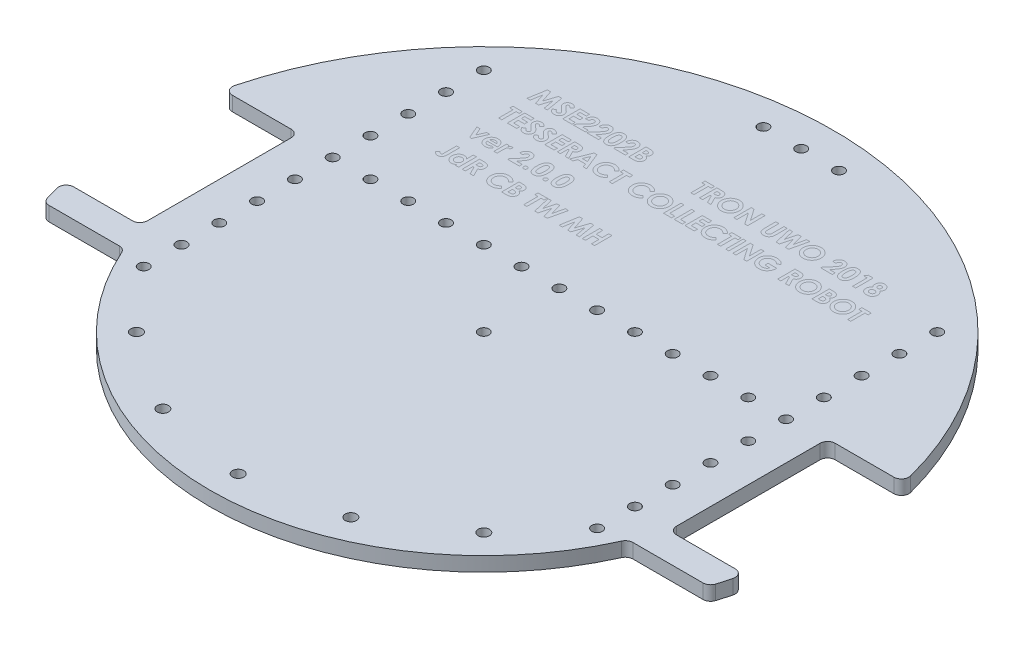
SolidWorks part; units mm, degrees
material "Balsa"
ref_plane "Front Plane" through (0, 0, 0) normal (0, 0, 1) x (1, 0, 0)
ref_plane "Top Plane" through (0, 0, 0) normal (0, 1, 0) x (1, 0, 0)
ref_plane "Right Plane" through (0, 0, 0) normal (1, 0, 0) x (0, 0, -1)
sketch "Sketch1" plane through (0, 0, 0) normal (0, 1, 0) x (1, 0, 0)
  circle A0 centre (0, 0) radius 117.475
  dimension "D1" = 234.95
extrude "Boss-Extrude1" add sketch "Sketch1" against normal blind 4.826
sketch "Sketch3" plane through (0, 0, 0) normal (0, 1, 0) x (1, 0, 0)
  line L1 (-114.4075, 26.67) -> (-88.9, 26.67)
  line L2 (0, -92.075) -> (0, -117.475)
  line L3 (-88.9, -26.67) -> (-88.9, 26.67)
  line L4 (0, 0) -> (-88.9, 0) construction
  line L5 (0, 0) -> (0, -117.475) construction
  line L6 (0, 0) -> (0, 117.475) construction
  line L8 (-88.9, -26.67) -> (-114.4075, -26.67)
  line L10 (-84.6624, -36.195) -> (-111.76, -36.195)
  arc A0 (-114.4075, 26.67) -> (-114.4075, -26.67) centre (0, 0) ccw
  circle A1 centre (0, 0) radius 117.475 construction
  arc A3 (-84.6624, -36.195) -> (0, -92.075) centre (0, 0) ccw
  arc A4 (-111.76, -36.195) -> (0, -117.475) centre (0, 0) ccw
  dimension "D1" = 88.9
  dimension "D2" = 53.34
  dimension "D4" = 9.525
  dimension "D5" = 25.4
extrude "Cut-Extrude4" cut sketch "Sketch3" against normal through all
fillet "Fillet1" radius 2.54 6 edges at (-114.4075, -2.413, 26.67) (-114.4075, -2.413, -26.67) (-88.9, -2.413, 26.67) (-88.9, -2.413, -26.67) (-111.76, -2.413, 36.195) (-84.6624, -2.413, 36.195)
mirror "Mirror1" about plane through (0, 0, 0) normal (1, 0, 0) of "Cut-Extrude4", "Fillet1"
sketch "Sketch4" plane through (0, 0, 0) normal (0, 1, 0) x (1, 0, 0)
  line L0 (-76.2, 38.1) -> (-76.2, 25.4) construction
  line L1 (-76.2, 25.4) -> (-76.2, 12.7) construction
  line L2 (-76.2, 12.7) -> (-76.2, 0) construction
  line L3 (-76.2, 0) -> (-76.2, -12.7) construction
  line L4 (-76.2, -12.7) -> (-76.2, -25.4) construction
  line L5 (-76.2, -25.4) -> (-76.2, -38.1) construction
  line L6 (0, 0) -> (-76.2, 0) construction
  line L12 (-76.2, 76.2) -> (-76.2, 63.5) construction
  line L13 (-76.2, 63.5) -> (-76.2, 50.8) construction
  line L14 (-76.2, 50.8) -> (-76.2, 38.1) construction
  circle A0 centre (-76.2, 0) radius 1.778
  circle A1 centre (-76.2, 12.7) radius 1.778
  circle A2 centre (-76.2, 25.4) radius 1.778
  circle A3 centre (-76.2, 38.1) radius 1.778
  circle A4 centre (-76.2, -12.7) radius 1.778
  circle A5 centre (-76.2, -25.4) radius 1.778
  circle A6 centre (-76.2, -38.1) radius 1.778
  circle A7 centre (-76.2, 50.8) radius 1.778
  circle A8 centre (-76.2, 63.5) radius 1.778
  circle A9 centre (-76.2, 76.2) radius 1.778
  dimension "D2" = 3.556
  dimension "D1" = 12.7
  dimension "D3" = 76.2
extrude "Cut-Extrude5" cut sketch "Sketch4" against normal through all
sketch "Sketch5" plane through (0, 0, 0) normal (0, 1, 0) x (1, 0, 0)
  circle A0 centre (0, 0) radius 1.778
  dimension "D1" = 3.556
extrude "Cut-Extrude6" cut sketch "Sketch5" against normal through all
sketch "Sketch6" plane through (0, 0, 0) normal (0, 1, 0) x (1, 0, 0)
  line L0 (0, 0) -> (0, 25.4) construction
  line L1 (0, 25.4) -> (12.7, 25.4) construction
  line L2 (12.7, 25.4) -> (25.4, 25.4) construction
  line L3 (25.4, 25.4) -> (38.1, 25.4) construction
  line L4 (-38.1, 25.4) -> (-50.8, 25.4) construction
  line L5 (38.1, 25.4) -> (50.8, 25.4) construction
  line L6 (0, 25.4) -> (-12.7, 25.4) construction
  line L7 (-12.7, 25.4) -> (-25.4, 25.4) construction
  line L8 (-25.4, 25.4) -> (-38.1, 25.4) construction
  line L9 (-50.8, 25.4) -> (-63.5, 25.4) construction
  line L10 (50.8, 25.4) -> (63.5, 25.4) construction
  line L11 (0, 106.68) -> (12.7, 106.68) construction
  line L12 (12.7, 106.68) -> (25.4, 106.68) construction
  line L13 (25.4, 106.68) -> (38.1, 106.68) construction
  line L14 (-38.1, 106.68) -> (-50.8, 106.68) construction
  line L15 (38.1, 106.68) -> (50.8, 106.68) construction
  line L16 (0, 106.68) -> (-12.7, 106.68) construction
  line L17 (-12.7, 106.68) -> (-25.4, 106.68) construction
  line L18 (-25.4, 106.68) -> (-38.1, 106.68) construction
  line L19 (-50.8, 106.68) -> (-63.5, 106.68) construction
  line L20 (50.8, 106.68) -> (63.5, 106.68) construction
  line L21 (0, 25.4) -> (0, 106.68) construction
  circle A0 centre (0, 25.4) radius 1.778
  circle A1 centre (-12.7, 25.4) radius 1.778
  circle A2 centre (-25.4, 25.4) radius 1.778
  circle A3 centre (-38.1, 25.4) radius 1.778
  circle A4 centre (12.7, 25.4) radius 1.778
  circle A5 centre (25.4, 25.4) radius 1.778
  circle A6 centre (38.1, 25.4) radius 1.778
  circle A7 centre (-50.8, 25.4) radius 1.778
  circle A8 centre (50.8, 25.4) radius 1.778
  circle A9 centre (-63.5, 25.4) radius 1.778
  circle A10 centre (63.5, 25.4) radius 1.778
  circle A11 centre (0, 106.68) radius 1.778
  circle A12 centre (-12.7, 106.68) radius 1.778
  circle A13 centre (-25.4, 106.68) radius 1.778 construction
  circle A14 centre (-38.1, 106.68) radius 1.778 construction
  circle A15 centre (12.7, 106.68) radius 1.778
  circle A16 centre (25.4, 106.68) radius 1.778 construction
  circle A17 centre (38.1, 106.68) radius 1.778 construction
  circle A18 centre (-50.8, 106.68) radius 1.778 construction
  circle A19 centre (50.8, 106.68) radius 1.778 construction
  circle A20 centre (-63.5, 106.68) radius 1.778 construction
  circle A21 centre (63.5, 106.68) radius 1.778 construction
  dimension "D1" = 3.556
  dimension "D4" = 3.556
  dimension "D2" = 12.7
  dimension "D3" = 25.4
  dimension "D5" = 12.7
  dimension "D6" = 81.28
extrude "Cut-Extrude7" cut sketch "Sketch6" against normal through all
mirror "Mirror3" about plane through (0, 0, 0) normal (1, 0, 0) of "Cut-Extrude5"
sketch "Sketch9" plane through (0, 0, 0) normal (0, 1, 0) x (1, 0, 0)
  line L4 (0, -82.55) -> (0, 0) construction
  circle A1 centre (0, -82.55) radius 1.905
  dimension "D2" = 3.81
  dimension "D1" = 82.55
extrude "Cut-Extrude10" cut sketch "Sketch9" against normal through all
pattern_circular "CirPattern1" count 3 over 45 about axis through (0, -4.826, 0) along (0, 1, 0) of "Cut-Extrude10"
pattern_circular "CirPattern2" count 3 over 45 about axis through (0, -4.826, 0) along (0, 1, 0) of "Cut-Extrude10" reverse direction yes
sketch "Sketch12" plane through (0, 0, 0) normal (0, 1, 0) x (1, 0, 0)
  text T0 "<b>MSE2202B       TRON UWO 2018</b>\r\n<b>TESSERACT COLLECTING ROBOT</b>\r\n<b>ver 2.0.0</b>\r\n<b>JdR CB TW MH</b>" font "Century Gothic" height 5.842
wrap "Wrap1" sketch "Sketch12" wrap type scribe source sketch "Sketch12" face at (-59.7187, 0, 59.7187)
sketch "Sketch7" plane through (0, 0, 0) normal (0, 1, 0) x (1, 0, 0)
  line L0 (-8.9803, 8.9803) -> (0, 0) construction
  line L1 (0, 0) -> (8.9803, -8.9803) construction
  line L3 (8.9803, 8.9803) -> (0, 0) construction
  line L4 (0, 0) -> (-8.9803, -8.9803) construction
  line L6 (-12.7, 0) -> (0, 0) construction
  line L7 (0, 0) -> (0, 12.7) construction
  line L9 (12.7, 0) -> (0, 0) construction
  line L10 (0, 0) -> (0, -12.7) construction
  circle A0 centre (0, 12.7) radius 1.778
  circle A1 centre (12.7, 0) radius 1.778
  circle A2 centre (0, -12.7) radius 1.778
  circle A3 centre (-12.7, 0) radius 1.778
  circle A4 centre (-8.9803, 8.9803) radius 1.778
  circle A5 centre (8.9803, 8.9803) radius 1.778
  circle A6 centre (8.9803, -8.9803) radius 1.778
  circle A7 centre (-8.9803, -8.9803) radius 1.778
  dimension "D1" = 45
  dimension "D2" = 3.556
  dimension "D3" = 12.7
extrude "Cut-Extrude8" [suppressed] cut sketch "Sketch7" against normal through all
sketch "Sketch8" plane through (0, 0, 0) normal (0, 1, 0) x (1, 0, 0)
  line L0 (0, 0) -> (-35.921, -35.921) construction
  line L1 (-35.921, -35.921) -> (-35.921, -1.2798) construction
  circle A0 centre (-35.921, -35.921) radius 12.7
  dimension "D3" = 25.4
  dimension "D1" = 45
  dimension "D2" = 50.8
extrude "Cut-Extrude9" [suppressed] cut sketch "Sketch8" against normal through all
sketch "Sketch10" plane through (0, 0, 0) normal (0, 1, 0) x (1, 0, 0)
  line L0 (-19.812, 85.09) -> (-19.812, 0) construction
  line L1 (-19.812, 0) -> (0, 0) construction
  circle A0 centre (-19.812, 85.09) radius 15.875
  dimension "D1" = 31.75
  dimension "D2" = 85.09
  dimension "D3" = 19.812
extrude "Cut-Extrude11" [suppressed] cut sketch "Sketch10" against normal through all
sketch "Sketch14" plane through (0, 0, 0) normal (0, 1, 0) x (1, 0, 0)
  line L0 (0, 0) -> (-55.6246, -77.3206) construction
  line L1 (-55.6246, -77.3206) -> (55.6246, -77.3206) construction
  line L2 (55.6246, -77.3206) -> (0, 0) construction
  arc A0 (-55.6246, -77.3206) -> (55.6246, -77.3206) centre (0, 0) ccw construction
  text T0 "<b>↑TESSERACTS↑</b>" font "Century Gothic" height 12.7
  dimension "D1" = 95.25
wrap "Wrap2" [suppressed] sketch "Sketch14" source sketch "Sketch14"
